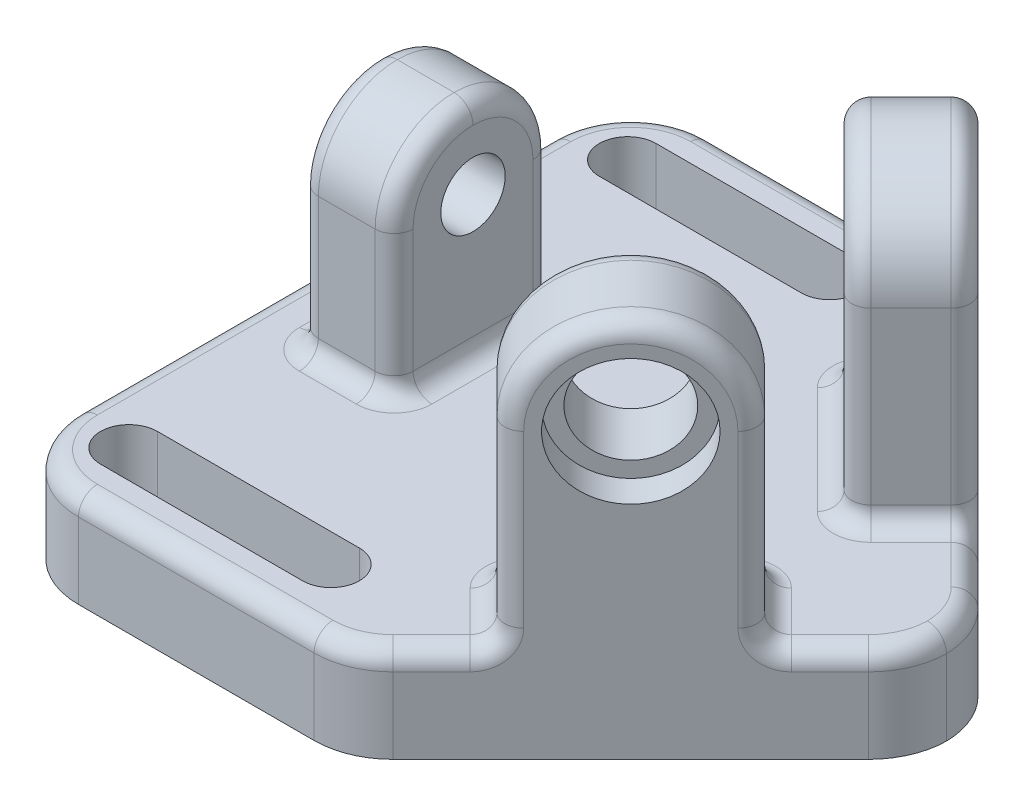
SolidWorks part; units mm, degrees
ref_plane "Plano frontal" through (0, 0, 0) normal (0, 0, 1) x (1, 0, 0)
ref_plane "Plano superior" through (0, 0, 0) normal (0, 1, 0) x (1, 0, 0)
ref_plane "Plano direito" through (0, 0, 0) normal (1, 0, 0) x (0, 0, -1)
sketch "Esboço1" plane through (0, 0, 0) normal (0, 1, 0) x (1, 0, 0)
  line L1 (-50, -50) -> (50, -50)
  line L2 (-50, -50) -> (-50, 50)
  line L3 (-50, 50) -> (50, 50)
  line L4 (50, -50) -> (50, 50)
  line L5 (-50, -50) -> (50, 50) construction
  line L6 (-50, 50) -> (50, -50) construction
  point P0 (0, 0)
  dimension "D1" = 100
  dimension "D2" = 100
extrude "Ressalto-extrusão1" add sketch "Esboço1" against normal blind 15
chamfer "Chanfro1" distance 45 angle 45 2 edges at (50, -7.5, -50) (50, -7.5, 50)
sketch "Esboço2" plane through (27.5, 0, 27.5) normal (0.7071, 0, 0.7071) x (0.7071, 0, -0.7071)
  line L0 (-15, 0) -> (15, 0)
  line L1 (-31.8198, 0) -> (31.8198, 0) construction
  line L2 (-31.8198, 0) -> (31.8198, 0)
  line L3 (-15, 30) -> (-15, 0)
  line L4 (15, 30) -> (15, 0)
  arc A0 (15, 30) -> (-15, 30) centre (0, 30) ccw
extrude "Ressalto-extrusão2" add sketch "Esboço2" against normal blind 15 contours L3 L0 L4 A0
hole_wizard "Rebaixo para parafuso Allen sextavado de M121" positions "Esboço3" profile "Esboço4" counterbore size "M12" standard "DIN" end condition up to next
sketch "Esboço3" plane through (27.5, 0, 27.5) normal (0.7071, 0, 0.7071) x (0.7071, 0, -0.7071)
  point P2 (0, 30)
sketch "Esboço4" plane through (27.5, 30, 27.5) normal (0, 1, 0) x (0.7071, 0, -0.7071)
  line L0 (0, 0) -> (0, 15)
  line L1 (0, 15) -> (7.5, 15)
  line L3 (7.5, 15) -> (7.5, 5)
  line L4 (7.5, 5) -> (10, 5)
  line L5 (10, 5) -> (10, 0)
  line L7 (10, 0) -> (0, 0)
  line L11 (0, -6.35) -> (0, 107.95) construction
  dimension "Thru Hole Dia." = 15
  dimension "Thru Hole Depth" = 15
  dimension "C'Bore Dia." = 20
  dimension "C'Bore Depth" = 5
mirror "Espelhar1" about plane through (0, 0, 0) normal (0, 0, 1) of "Rebaixo para parafuso Allen sextavado de M121", "Ressalto-extrusão2"
sketch "Esboço6" plane through (0, 0, 0) normal (0, 1, 0) x (1, 0, 0)
  line L0 (-50, 50) -> (-50, -50) construction
  line L1 (-25, 12.5) -> (-40, 12.5)
  line L2 (-25, 12.5) -> (-25, -12.5)
  line L3 (-25, -12.5) -> (-40, -12.5)
  line L4 (-40, 12.5) -> (-40, -12.5)
  line L5 (-25, 12.5) -> (-40, -12.5) construction
  line L6 (-25, -12.5) -> (-40, 12.5) construction
  point P0 (-32.5, 0)
  point P5 (-25, 0)
  dimension "D1" = 15
  dimension "D2" = 25
  dimension "D3" = 10
extrude "Ressalto-extrusão3" add sketch "Esboço6" along normal blind 35
fillet "Filete1" radius 12.5 2 edges at (-32.5, 35, -12.5) (-32.5, 35, 12.5)
hole_wizard "Furo roscado de M121" positions "Esboço7" profile "Esboço8" tap size "M12" standard "DIN" end condition up to next
sketch "Esboço7" plane through (-40, 0, 0) normal (-1, 0, 0) x (0, 0, 1)
  point P0 (0, 22.5)
sketch "Esboço8" plane through (-40, 22.5, 0) normal (0, 1, 0) x (0, 0, 1)
  line L0 (0, 0) -> (0, 15)
  line L1 (0, 15) -> (5.1, 15)
  line L2 (5.1, 15) -> (5.1, 0)
  line L5 (5.1, 0) -> (0, 0)
  line L11 (0, -6.35) -> (0, 107.95) construction
  dimension "Thru Tap Drill Dia." = 10.2
  dimension "Thru Tap Drill Depth" = 15
cosmetic thread "Rosca de furo1" parameters "D2"=12
sketch "Esboço9" plane through (0, 0, 0) normal (0, 1, 0) x (1, 0, 0)
  line L0 (-8, 39.5) -> (-40, 39.5) construction
  line L1 (-8, 35) -> (-40, 35)
  line L2 (-8, 44) -> (-40, 44)
  line L3 (-50, 50) -> (-50, -50) construction
  arc A0 (-8, 35) -> (-8, 44) centre (-8, 39.5) ccw
  arc A1 (-40, 44) -> (-40, 35) centre (-40, 39.5) ccw
  point P2 (-24, 39.5)
  dimension "D1" = 4.5
  dimension "D2" = 35
  dimension "D3" = 32
  dimension "D4" = 10
extrude "Corte-extrusão1" cut sketch "Esboço9" against normal blind 35
mirror "Espelhar2" about plane through (0, 0, 0) normal (0, 0, 1) of "Corte-extrusão1"
fillet "Filete2" radius 12.5 3 edges at (5, -7.5, 50) (-50, -7.5, -50) (-50, -7.5, 50)
fillet "Filete4" radius 12.5 3 edges at (5, -7.5, -50) (50, -7.5, -5) (50, -7.5, 5)
fillet "Filete5" radius 3 43 edges at (49.0142, 0, -4.6878) (42.2227, 0, -12.7773) (38.1066, 15, -16.8934) (27.5, 45, -27.5) (16.8934, 15, -38.1066) (12.7773, 0, -42.2227) (4.6059, 0, -49.0485) (-18.8388, 0, -50) (-46.3388, 0, -46.3388) (-50, 0, 0) (-46.3388, 0, 46.3388) (-18.8388, 0, 50) (49.0142, 0, 4.6878) (4.6059, 0, 49.0485) (42.2227, 0, 12.7773) (12.7773, 0, 42.2227) (38.1066, 15, 16.8934) (16.8934, 15, 38.1066) (27.5, 15, -6.2868) (16.8934, 0, -16.8934) (6.2868, 15, -27.5) (16.8934, 45, -16.8934) (-40, 11.25, 12.5) (-40, 0, 0) (-40, 11.25, -12.5) (-40, 31.3388, -8.8388) (-40, 31.3388, 8.8388) (-25, 0, 0) (-25, 11.25, 12.5) (-25, 31.3388, 8.8388) (-25, 31.3388, -8.8388) (-25, 11.25, -12.5) (6.2868, 15, 27.5) (16.8934, 0, 16.8934) (27.5, 15, 6.2868) (16.8934, 45, 16.8934) (27.5, 45, 27.5) (-32.5, 0, 12.5) (11.5901, 0, 32.8033) (-32.5, 0, -12.5) (11.5901, 0, -32.8033) (32.8033, 0, -11.5901) (32.8033, 0, 11.5901)
